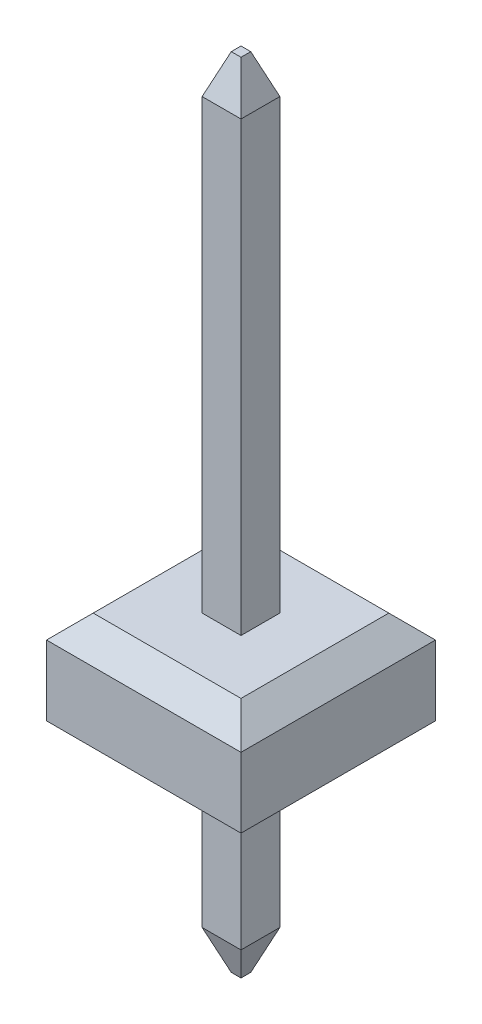
SolidWorks part; units mm, degrees
ref_plane "Front Plane" through (0, 0, 0) normal (0, 0, 1) x (1, 0, 0)
ref_plane "Top Plane" through (0, 0, 0) normal (0, 1, 0) x (1, 0, 0)
ref_plane "Right Plane" through (0, 0, 0) normal (1, 0, 0) x (0, 0, -1)
sketch "Sketch1" plane through (0, 0, 0) normal (0, 1, 0) x (1, 0, 0)
  line L1 (0, 0) -> (2.54, 0)
  line L2 (0, 0) -> (0, 2.54)
  line L3 (0, 2.54) -> (2.54, 2.54)
  line L4 (2.54, 0) -> (2.54, 2.54)
  dimension "D1" = 2.54
  dimension "D2" = 2.54
extrude "Boss-Extrude1" add sketch "Sketch1" along normal blind 1.524
sketch "Sketch2" plane through (0, 1.524, 0) normal (0, 1, 0) x (1, 0, 0)
  line L0 (0, 2.54) -> (0, 0) construction
  line L1 (0, 0) -> (2.54, 0) construction
  line L2 (1.27, 0) -> (1.27, 2.0363) construction
  line L3 (1.524, 1.524) -> (1.016, 1.524)
  line L4 (1.524, 1.524) -> (1.524, 1.016)
  line L5 (1.524, 1.016) -> (1.016, 1.016)
  line L6 (1.016, 1.524) -> (1.016, 1.016)
  line L7 (1.524, 1.524) -> (1.016, 1.016) construction
  line L8 (1.524, 1.016) -> (1.016, 1.524) construction
  line L9 (0, 1.27) -> (2.1183, 1.27) construction
  point P0 (0, 1.27)
  point P1 (1.27, 0)
  point P4 (1.27, 1.27)
  point P7 (1.27, 1.27)
  dimension "D1" = 0.508
  dimension "D2" = 0.508
  dimension "D3" = 0
  dimension "D4" = 0
extrude "Boss-Extrude2" add sketch "Sketch2" along normal blind 6.35
sketch "Sketch3" plane through (0, 0, 0) normal (0, -1, 0) x (1, 0, 0)
  line L4 (1.016, -1.016) -> (1.016, -1.524)
  line L5 (1.524, -1.016) -> (1.016, -1.016)
  line L6 (1.524, -1.524) -> (1.524, -1.016)
  line L7 (1.016, -1.524) -> (1.524, -1.524)
  line L8 (1.016, -1.016) -> (1.016, -1.524)
  line L9 (1.524, -1.016) -> (1.016, -1.016)
  line L10 (1.524, -1.524) -> (1.524, -1.016)
  line L11 (1.016, -1.524) -> (1.524, -1.524)
  dimension "D1" = 0
extrude "Boss-Extrude3" add sketch "Sketch3" along normal blind 2.54
chamfer "Chamfer1" distance 0.508 distance2 0.1905 4 edges at (1.524, 7.874, -1.27) (1.27, 7.874, -1.524) (1.016, 7.874, -1.27) (1.27, 7.874, -1.016) first distance on face at (1.524, 4.699, -1.27) first distance on face at (1.27, 4.699, -1.524) first distance on face at (1.016, 4.699, -1.27) first distance on face at (1.27, 4.699, -1.016)
chamfer "Chamfer2" distance 0.508 distance2 0.1905 4 edges at (1.524, -2.54, -1.27) (1.27, -2.54, -1.524) (1.016, -2.54, -1.27) (1.27, -2.54, -1.016) first distance on face at (1.524, -1.27, -1.27) first distance on face at (1.27, -1.27, -1.524) first distance on face at (1.016, -1.27, -1.27) first distance on face at (1.27, -1.27, -1.016)
chamfer "Chamfer4" distance 0.3048 angle 45 4 edges at (2.54, 1.524, -1.27) (1.27, 1.524, -2.54) (0, 1.524, -1.27) (1.27, 1.524, 0)
chamfer "Chamfer5" distance 0.3048 angle 45 4 edges at (2.54, 0, -1.27) (1.27, 0, -2.54) (0, 0, -1.27) (1.27, 0, 0)
